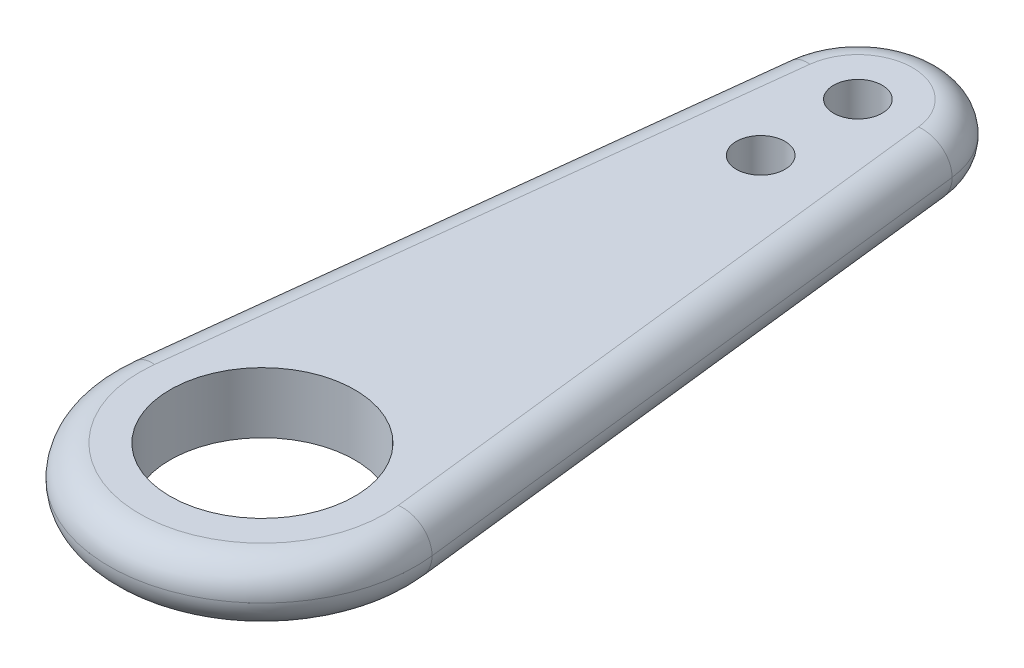
SolidWorks part; units mm, degrees
ref_plane "Alzado" through (0, 0, 0) normal (0, 0, 1) x (1, 0, 0)
ref_plane "Planta" through (0, 0, 0) normal (0, 1, 0) x (1, 0, 0)
ref_plane "Vista lateral" through (0, 0, 0) normal (1, 0, 0) x (0, 0, -1)
sketch "Croquis2" plane through (0, 0, 0) normal (0, 1, 0) x (1, 0, 0)
  line L0 (-2.7817, 3.52) -> (-5.007, -15.824)
  line L1 (0, 3.2) -> (0, -16.4) construction
  line L2 (2.7817, 3.52) -> (5.007, -15.824)
  circle A0 centre (0, 0) radius 0.8
  circle A1 centre (0, 3.2) radius 0.8
  circle A2 centre (0, -16.4) radius 3.04
  arc A3 (-5.007, -15.824) -> (5.007, -15.824) centre (0, -16.4) ccw
  arc A4 (2.7817, 3.52) -> (-2.7817, 3.52) centre (0, 3.2) ccw
  circle A6 centre (0, 3.2) radius 2.8 construction
  circle A7 centre (0, -16.4) radius 5.04 construction
  point P10 (5.04, -7)
  point P15 (2.6777, 4.0186)
  dimension "D1" = 3.2
  dimension "D2" = 1.6
  dimension "D3" = 1.6
  dimension "D4" = 6.08
  dimension "D5" = 16.4
  dimension "D6" = 2
  dimension "D7" = 2
extrude "Saliente-Extruir1" add sketch "Croquis2" along normal mid plane 2
fillet "Redondeo1" radius 1 8 edges at (-3.8943, -1, 6.152) (0, -1, -6) (3.8943, -1, 6.152) (-3.8943, 1, 6.152) (0, 1, -6) (3.8943, 1, 6.152) (0, -1, 21.44) (0, 1, 21.44)
